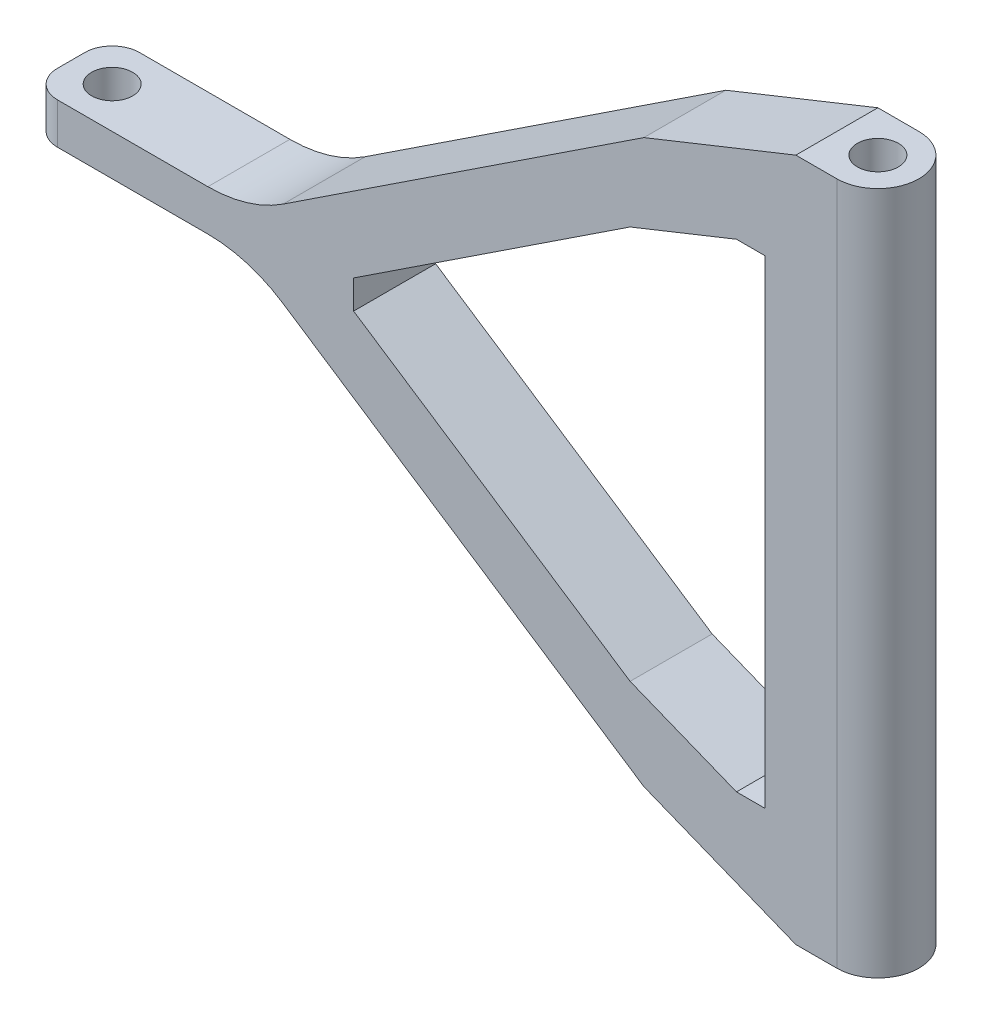
SolidWorks part; units mm, degrees
ref_plane "Front Plane" through (0, 0, 0) normal (0, 0, 1) x (1, 0, 0)
ref_plane "Top Plane" through (0, 0, 0) normal (0, 1, 0) x (1, 0, 0)
ref_plane "Right Plane" through (0, 0, 0) normal (1, 0, 0) x (0, 0, -1)
sketch "Sketch1" plane through (0, 0, 0) normal (0, 1, 0) x (1, 0, 0)
  line L0 (0, 3) -> (-3, 3)
  line L1 (-3, 3) -> (-3, -3)
  line L2 (-3, -3) -> (0, -3)
  circle A0 centre (0, 0) radius 1.5
  arc A1 (0, -3) -> (0, 3) centre (0, 0) ccw
  dimension "D1" = 3
  dimension "D2" = 6
  dimension "D3" = 6
  dimension "D4" = 3
extrude "Boss-Extrude1" add sketch "Sketch1" along normal blind 50
sketch "Sketch2" plane through (-3, 0, 0) normal (-1, 0, 0) x (0, 0, 1)
  line L1 (-3, 0) -> (3, 0)
  line L2 (-3, 0) -> (-3, 50)
  line L3 (-3, 50) -> (3, 50)
  line L4 (3, 0) -> (3, 50)
  line L5 (-3, 0) -> (3, 50) construction
  line L6 (-3, 50) -> (3, 0) construction
  point P0 (0, 25)
extrude "Boss-Extrude2" add sketch "Sketch2" along normal blind 50
chamfer "Chamfer1" distance 50 distance2 20 2 edges at (-53, 0, 0) (-53, 50, 0) first distance on face at (-25.75, 0, 0) first distance on face at (-25.75, 50, 0)
sketch "Sketch4" plane through (-53, 0, 0) normal (-1, 0, 0) x (0, 0, 1)
  line L0 (3, 20) -> (3, 30) construction
  line L1 (-3, 23.5) -> (3, 23.5)
  line L2 (-3, 23.5) -> (-3, 26.5)
  line L3 (-3, 26.5) -> (3, 26.5)
  line L4 (3, 23.5) -> (3, 26.5)
  line L5 (-3, 23.5) -> (3, 26.5) construction
  line L6 (-3, 26.5) -> (3, 23.5) construction
  line L7 (-3, 30) -> (-3, 20) construction
  line L9 (3, 25) -> (-5.4605, 25) construction
  point P0 (0, 25)
  dimension "D1" = 3
extrude "Boss-Extrude3" add sketch "Sketch4" along normal blind 6
sketch "Sketch5" plane through (0, 23.5, 0) normal (0, -1, 0) x (1, 0, 0)
  line L0 (-59, 3) -> (-53, 3) construction
  line L1 (-59, -3) -> (-59, 3) construction
  circle A0 centre (-56, 0) radius 1.5
  dimension "D1" = 3
  dimension "D2" = 3
  dimension "D3" = 3
extrude "Cut-Extrude1" cut sketch "Sketch5" against normal through all
chamfer "Chamfer2" distance 1 angle 45 2 edges at (-53, 30, 0) (-53, 20, 0) first distance on face at (-28, 40, 0) first distance on face at (-28, 10, 0)
fillet "Fillet1" radius 2 2 edges at (-59, 25, -3) (-59, 25, 3)
sketch "Sketch6" plane through (0, 0, 3) normal (0, 0, 1) x (1, 0, 0)
  line L0 (-7.9072, 5) -> (-5.5072, 5)
  line L1 (-5.5072, 45) -> (-7.9072, 45)
  line L2 (-5.5072, 5) -> (-5.5072, 45)
  line L3 (-47.1644, 29.2971) -> (-47.9072, 27.564)
  line L4 (-47.9072, 22.436) -> (-47.1644, 20.7029)
  line L5 (-7.9072, 45) -> (-47.1644, 29.2971)
  line L6 (-47.9072, 27.564) -> (-47.9072, 22.436)
  line L7 (-47.1644, 20.7029) -> (-7.9072, 5)
  line L12 (-53, 26.5) -> (-57, 26.5)
  line L13 (-57, 26.5) -> (-57, 23.5)
  line L14 (-57, 23.5) -> (-53, 23.5)
  line L15 (-53, 23.5) -> (-53, 21.7951)
  line L16 (-53, 21.7951) -> (-52.0715, 19.6286)
  line L17 (-52.0715, 19.6286) -> (-3, 0)
  line L18 (-3, 0) -> (0, 0)
  line L19 (0, 0) -> (0, 50)
  line L20 (0, 50) -> (-3, 50)
  line L21 (-3, 50) -> (-52.0715, 30.3714)
  line L22 (-52.0715, 30.3714) -> (-53, 28.2049)
  line L23 (-53, 28.2049) -> (-53, 26.5)
  line L24 (-53, 26.5) -> (-57, 26.5)
  line L25 (-57, 26.5) -> (-57, 23.5)
  line L26 (-57, 23.5) -> (-53, 23.5)
  line L27 (-53, 23.5) -> (-53, 21.7951)
  line L28 (-53, 21.7951) -> (-52.0715, 19.6286)
  line L29 (-52.0715, 19.6286) -> (-3, 0)
  line L30 (-3, 0) -> (0, 0)
  line L31 (0, 0) -> (0, 50)
  line L32 (0, 50) -> (-3, 50)
  line L33 (-3, 50) -> (-52.0715, 30.3714)
  line L34 (-52.0715, 30.3714) -> (-53, 28.2049)
  line L35 (-53, 28.2049) -> (-53, 26.5)
  dimension "D1" = 0
extrude "Cut-Extrude2" cut sketch "Sketch6" against normal blind 6 contours L3 L6 L4 L7 L0 L2 L1 L5
sketch "Sketch7" plane through (0, 0, 3) normal (0, 0, 1) x (1, 0, 0)
  line L0 (-53, 26.5) -> (-43, 26.5)
  line L1 (-53, 23.5) -> (-43, 23.5)
  line L2 (-43, 26.5) -> (-14.1124, 45.555)
  line L3 (-3, 50) -> (-52.0715, 30.3714) construction
  line L4 (-43, 23.5) -> (-14.1124, 4.445)
  line L5 (-52.0715, 19.6286) -> (-3, 0) construction
  line L6 (-14.1124, 4.445) -> (-3, 0)
  line L7 (-3, 0) -> (-3, 50)
  line L8 (-3, 50) -> (-14.1124, 45.555)
  line L9 (-53, 26.5) -> (-53, 23.5)
  line L10 (-14.1124, 45.555) -> (-64.5165, 45.555)
  line L11 (-64.5165, 45.555) -> (-64.5165, 0.8769)
  line L12 (-64.5165, 0.8769) -> (-14.1124, 4.445)
  line L13 (-53, 26.5) -> (-59.9638, 45.555)
  line L14 (-53, 23.5) -> (-59.9638, 1.1992)
  dimension "D1" = 10
  dimension "D2" = 10
extrude "Cut-Extrude3" cut sketch "Sketch7" against normal through all contours L11 L2 L0 L8 | L4 L6 L7 L8 L1 L13 L14 region at (-41.3463, 38.0661, 3) region at (-41.4537, 10.9046, 3)
extrude "Boss-Extrude5" add sketch "Sketch7<3>" against normal up to surface (6 mm away) contours L1 L4 L6 L5 L3 L11 L2 L0 L8 region at (-18.0879, 25, 3) up to face at (-52.4536, 25, -3)
sketch "Sketch7<3>" plane through (0, 0, 3) normal (0, 0, 1) x (1, 0, 0) same geometry as "Sketch7"
sketch "Sketch8" plane through (0, 0, 3) normal (0, 0, 1) x (1, 0, 0)
  line L0 (-3, 50) -> (0, 50) construction
  line L1 (-3, 50) -> (-14.1124, 45.555) construction
  line L2 (0, 50) -> (0, 0) construction
  line L3 (-3, 0) -> (0, 0) construction
  line L4 (-14.1124, 4.445) -> (-3, 0) construction
  line L5 (-43, 23.5) -> (-14.1124, 4.445) construction
  line L6 (-43, 26.5) -> (-14.1124, 45.555) construction
  line L7 (-3, 50) -> (0, 50)
  line L8 (-3, 50) -> (-14.1124, 45.555)
  line L9 (0, 50) -> (0, 0)
  line L10 (-3, 0) -> (0, 0)
  line L11 (-14.1124, 4.445) -> (-3, 0)
  line L12 (-43, 23.5) -> (-14.1124, 4.445)
  line L13 (-43, 26.5) -> (-14.1124, 45.555)
  line L14 (-7.3416, 42.5) -> (-5.2416, 42.5)
  line L15 (-15.1202, 10.6115) -> (-7.3416, 7.5)
  line L16 (-5.2416, 42.5) -> (-5.2416, 7.5)
  line L17 (-35.3416, 23.95) -> (-15.1202, 10.6115)
  line L18 (-7.3416, 7.5) -> (-5.2416, 7.5)
  line L19 (-7.3416, 42.5) -> (-15.1202, 39.3885)
  line L20 (-35.3416, 26.05) -> (-15.1202, 39.3885)
  line L21 (-35.3416, 26.05) -> (-35.3416, 23.95)
extrude "Cut-Extrude4" cut sketch "Sketch8" against normal through all contours L20 L21 L17 L15 L18 L16 L14 L19 region at (-16.0707, 25, 3)
fillet "Fillet2" radius 10 2 edges at (-43, 26.5, 0) (-43, 23.5, 0)
